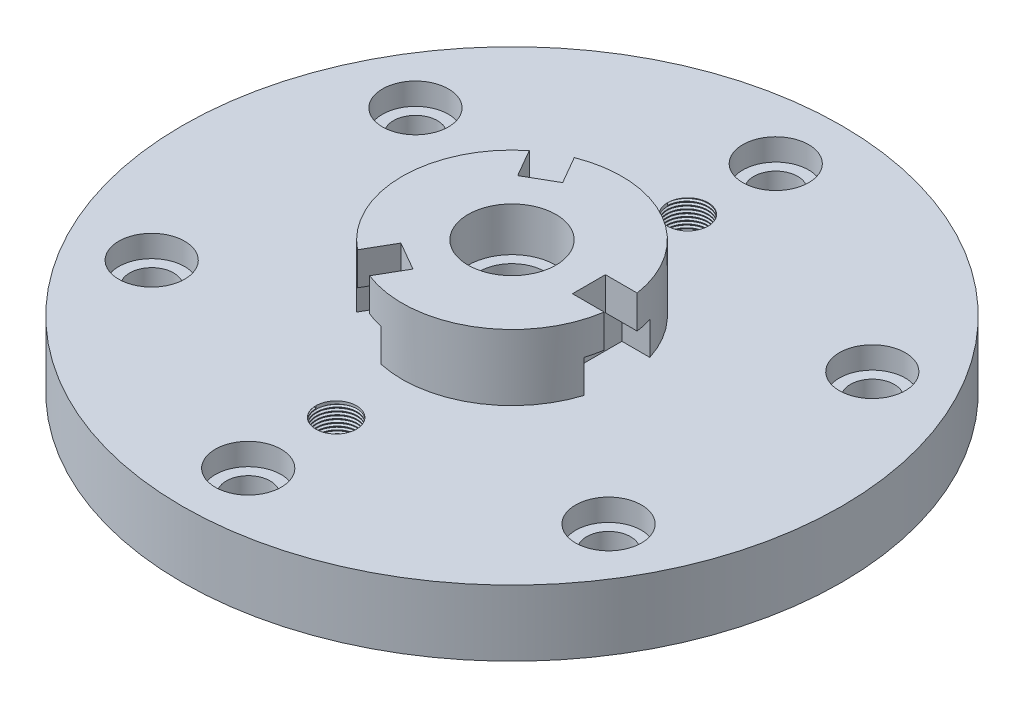
SolidWorks part; units mm, degrees
material "Cast Alloy Steel"
ref_plane "Front Plane" through (0, 0, 0) normal (0, 0, 1) x (1, 0, 0)
ref_plane "Top Plane" through (0, 0, 0) normal (0, 1, 0) x (1, 0, 0)
ref_plane "Right Plane" through (0, 0, 0) normal (1, 0, 0) x (0, 0, -1)
sketch "Sketch1" plane through (0, 0, 0) normal (0, 0, 1) x (1, 0, 0)
  line L0 (0, -100) -> (0, 30) construction
  line L1 (15, 10) -> (20, 10)
  line L2 (-15, 10) -> (-20, 10)
  line L3 (20, 10) -> (20, 30)
  line L4 (-20, 10) -> (-20, 30)
  line L5 (20, 30) -> (50, 30)
  line L6 (-20, 30) -> (-50, 30)
  line L7 (50, 30) -> (50, 0)
  line L8 (-50, 30) -> (-50, 0)
  line L9 (50, 0) -> (150, 0)
  line L10 (-50, 0) -> (-150, 0)
  line L11 (150, 0) -> (150, -30)
  line L12 (-150, 0) -> (-150, -30)
  line L13 (150, -30) -> (65, -30)
  line L14 (-150, -30) -> (-60, -30)
  line L15 (60, -35) -> (60, -45)
  line L16 (-60, -30) -> (-60, -50)
  line L17 (55, -50) -> (40, -50)
  line L18 (-60, -50) -> (-30, -50)
  line L19 (30, -60) -> (30, -100)
  line L20 (-30, -50) -> (-30, -100)
  line L21 (30, -100) -> (15, -100)
  line L22 (-30, -100) -> (-15, -100)
  line L23 (15, -100) -> (15, 10)
  line L24 (-15, -100) -> (-15, 10)
  arc A0 (60, -45) -> (55, -50) centre (55, -45) cw
  arc A1 (65, -30) -> (60, -35) centre (65, -35) ccw
  arc A2 (40, -50) -> (30, -60) centre (40, -60) ccw
  point P6 (0, -35)
  point P34 (60, -50)
  point P37 (60, -30)
  point P40 (30, -50)
  dimension "D12" = 5
  dimension "D13" = 10
  dimension "D1" = 40
  dimension "D2" = 20
  dimension "D3" = 30
  dimension "D4" = 30
  dimension "D5" = 20
  dimension "D6" = 50
  dimension "D7" = 300
  dimension "D8" = 30
  dimension "D9" = 100
  dimension "D10" = 120
  dimension "D11" = 60
revolve "Revolve1" add sketch "Sketch1" angle 360 about L0
sketch "Sketch2" plane through (0, 0, 0) normal (1, 0, 0) x (0, 0, -1)
  line L0 (0, 0) -> (0, 30) construction
  line L1 (50, 30) -> (-50, 30) construction
  line L2 (-7.5, 30) -> (7.5, 30)
  line L3 (20, 30) -> (-20, 30) construction
  line L4 (7.5, 30) -> (7.5, 15)
  line L5 (-7.5, 30) -> (-7.5, 15)
  line L6 (7.5, 15) -> (15, 15)
  line L7 (-7.5, 15) -> (-15, 15)
  line L8 (15, 15) -> (15, 0)
  line L9 (150, 0) -> (-150, 0) construction
  line L10 (-15, 15) -> (-15, 0)
  line L11 (15, 0) -> (-15, 0)
  dimension "D1" = 15
  dimension "D2" = 30
extrude "Cut-Extrude1" cut sketch "Sketch2" along normal through all from offset 35
pattern_circular "CirPattern1" count 3 over 360 about axis through (0, 0, 0) along (0, 1, 0) of "Cut-Extrude1"
sketch "Sketch6" plane through (0, 0, 0) normal (0, 1, 0) x (1, 0, 0)
  point P2 (0, 120)
  point P6 (0, 0)
  dimension "D1" = 120
hole_wizard "CBORE for M20 Hex Head Bolt1" positions "Sketch6" profile "Sketch5" counterbore size "M20" standard "DIN" end condition through all
sketch "Sketch5" plane through (0, 0, -120) normal (1, 0, 0) x (0, 0, 1)
  line L0 (0, 0) -> (0, 100)
  line L1 (0, 100) -> (10, 100)
  line L3 (10, 100) -> (10, 10)
  line L4 (10, 10) -> (15, 10)
  line L5 (15, 10) -> (15, 0)
  line L7 (15, 0) -> (0, 0)
  line L11 (0, -6.35) -> (0, 107.95) construction
  dimension "Thru Hole Dia." = 20
  dimension "Thru Hole Depth" = 100
  dimension "C'Bore Dia." = 30
  dimension "C'Bore Depth" = 10
pattern_circular "CirPattern2" count 6 over 360 about axis through (0, 0, 0) along (0, 1, 0) of "CBORE for M20 Hex Head Bolt1"
sketch "Sketch9" plane through (0, 0, 0) normal (0, 1, 0) x (1, 0, 0)
  point P0 (0, 80)
  point P5 (0, 80)
  dimension "D1" = 80
hole_wizard "Tap Drill for M20x1.5 Tap1" positions "Sketch9" profile "Sketch10" hole size "M20x1.5" standard "DIN" end condition through all
sketch "Sketch10" plane through (0, 0, -80) normal (1, 0, 0) x (0, 0, 1)
  line L0 (0, 0) -> (0, 100)
  line L1 (0, 100) -> (9.25, 100)
  line L2 (9.25, 100) -> (9.25, 0)
  line L5 (9.25, 0) -> (0, 0)
  line L11 (0, -6.35) -> (0, 107.95) construction
  dimension "Thru Hole Dia." = 18.5
  dimension "Thru Hole Depth" = 100
thread "Thread1" pitch 1.5 start angle 0, offset 0, length 0, pitch 1.5, diameter 18.5
ref_plane "Plane1" through (-9.25, 0, -80) normal (0, 0, 1) x (-1, 0, 0)
sketch "Thread Profile1" plane through (-9.25, 0, -80) normal (0, 0, 1) x (-1, 0, 0)
  line L0 (0, 0) -> (0, 1.5) construction
  line L1 (0, 0) -> (0.8119, 0.4687)
  line L2 (0.8119, 0.4687) -> (0.8119, 0.6562)
  line L3 (0.8119, 0.6562) -> (0, 1.125)
  line L4 (0.8119, 0.5625) -> (0, 0.5625) construction
  line L11 (0, 0) -> (0, 1.125)
  point P2 (0, 0)
  dimension "Pitch" = 1.5
  dimension "Profile_Angle" = 60
  dimension "Profile_Land" = 0.1875
  dimension "Profile_Height" = 0.8119
mirror "Mirror1" about plane through (0, 0, 0) normal (0, 0, 1) of "Thread1", "Tap Drill for M20x1.5 Tap1"
sketch "Sketch15" plane through (0, 0, 0) normal (1, 0, 0) x (0, 0, -1)
  line L0 (-8, -100) -> (-8, -70)
  line L1 (-30, -100) -> (30, -100) construction
  line L2 (8, -70) -> (8, -100)
  line L3 (8, -100) -> (-8, -100)
  arc A0 (-8, -70) -> (8, -70) centre (0, -70) cw
  point P6 (0, -62)
  dimension "D2" = 30
  dimension "D1" = 16
extrude "Cut-Extrude4" cut sketch "Sketch15" along normal through all from offset 25
mirror "Mirror2" about plane through (0, 0, 0) normal (1, 0, 0) of "Cut-Extrude4"
